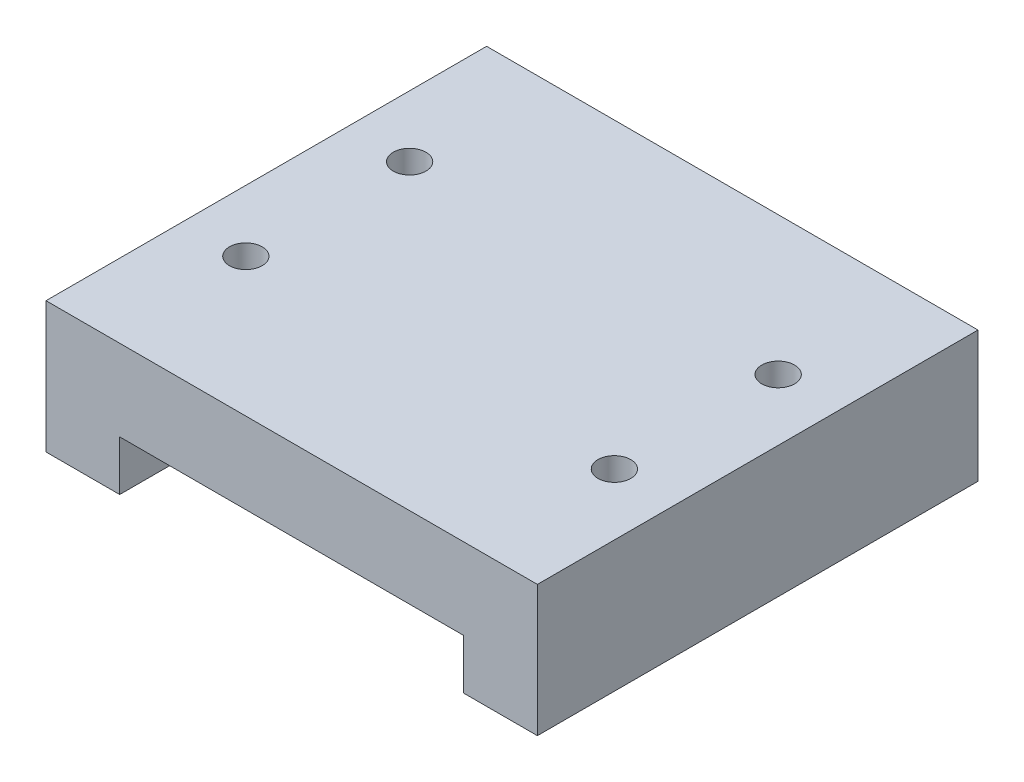
SolidWorks part; units mm, degrees
ref_plane "前基準面" through (0, 0, 0) normal (0, 0, 1) x (1, 0, 0)
ref_plane "上基準面" through (0, 0, 0) normal (0, 1, 0) x (1, 0, 0)
ref_plane "右基準面" through (0, 0, 0) normal (1, 0, 0) x (0, 0, -1)
sketch "草圖1" plane through (0, 0, 0) normal (0, 0, 1) x (1, 0, 0)
  line L0 (0, 8) -> (0, -8) construction
  line L1 (-30, 8) -> (30, 8)
  line L2 (-30, 8) -> (-30, -8)
  line L3 (-30, -8) -> (30, -8)
  line L4 (30, 8) -> (30, -8)
  line L5 (-30, 8) -> (30, -8) construction
  line L6 (-30, -8) -> (30, 8) construction
  line L7 (-21, -8) -> (-21, -1.9)
  line L8 (-21, -1.9) -> (21, -1.9)
  line L9 (21, -8) -> (21, -1.9)
  line L10 (-21, -8) -> (21, -8)
  point P0 (0, 0)
  point P12 (0, -1.9)
  dimension "D1" = 60
  dimension "D2" = 16
  dimension "D3" = 9
  dimension "D4" = 6.1
extrude "填料-伸長1" add sketch "草圖1" along normal blind 53.8 contours L9 L3 L4 L1 L2 L7 L8 region at (0, 1.8019, 0)
sketch "草圖2" plane through (0, 8, 0) normal (0, 1, 0) x (1, 0, 0)
  line L0 (0, 0) -> (0, -53.8) construction
  line L1 (-30, -53.8) -> (30, -53.8) construction
  line L2 (-22.5, 0) -> (-22.5, -53.8) construction
  line L3 (-30, 0) -> (30, 0) construction
  line L4 (-30, -53.8) -> (-30, 0) construction
  line L5 (-30, -26.9) -> (30, -26.9) construction
  line L6 (30, -53.8) -> (30, 0) construction
  line L7 (-28.4, 0) -> (-28.4, -53.8) construction
  circle A0 centre (-22.5, -16.9) radius 2
  circle A1 centre (-22.5, -36.9) radius 2
  circle A2 centre (22.5, -36.9) radius 2
  circle A3 centre (22.5, -16.9) radius 2
  dimension "D2" = 4
  dimension "D6" = 16.9
  dimension "D1" = 22.5
  dimension "D3" = 10
  dimension "D4" = 7.5
  dimension "D5" = 1.6
extrude "除料-伸長1" cut sketch "草圖2" against normal blind 4.2
